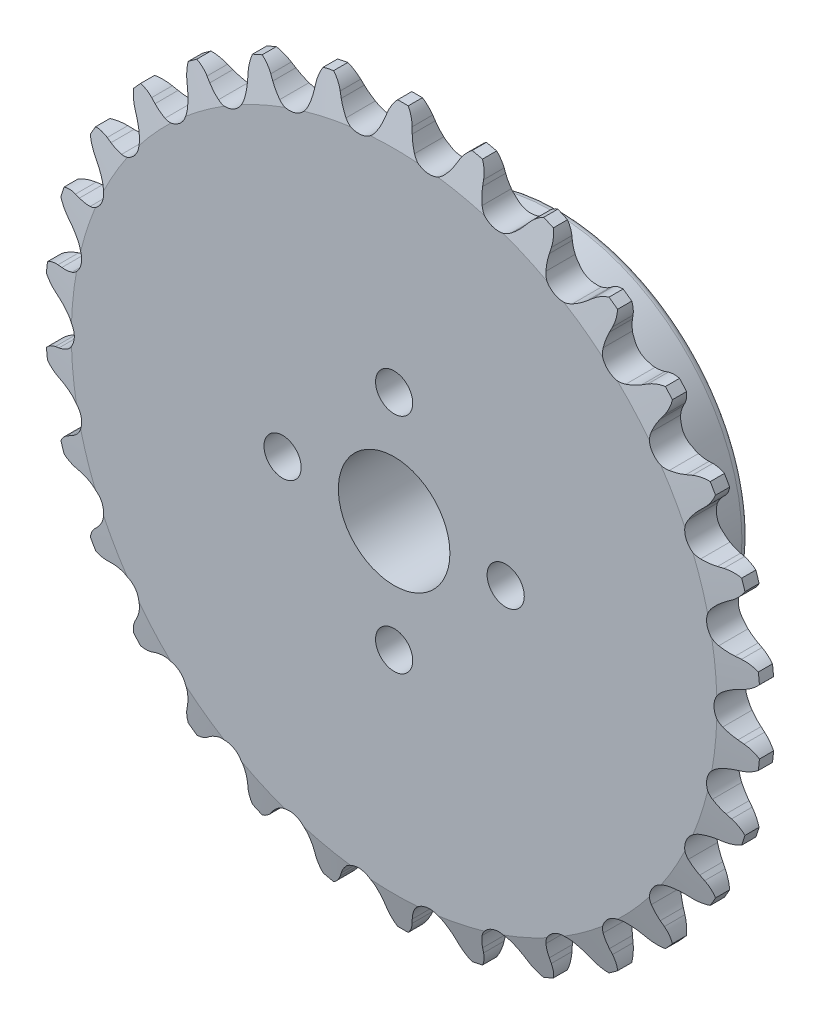
SolidWorks part; units mm, degrees
ref_plane "Front Plane" through (0, 0, 0) normal (0, 0, 1) x (1, 0, 0)
ref_plane "Top Plane" through (0, 0, 0) normal (0, 1, 0) x (1, 0, 0)
ref_plane "Right Plane" through (0, 0, 0) normal (1, 0, 0) x (0, 0, -1)
sketch "Sketch0" plane through (0, 0, 0) normal (0, 0, 1) x (1, 0, 0)
  line L0 (4.7625, -45.3122) -> (0, 0) construction
  line L1 (0, 0) -> (14.0794, -43.3318) construction
  line L2 (0, 0) -> (-4.7625, -45.3122) construction
  line L3 (4.7625, -45.3122) -> (14.0794, -43.3318) construction
  line L4 (4.7625, -45.3122) -> (-4.7625, -45.3122) construction
  line L5 (8.0084, -45.7133) -> (7.6941, -45.0929)
  line L6 (4.7625, -45.3122) -> (0, -45.8127) construction
  line L7 (1.6709, -46.3794) -> (1.8494, -45.7072)
  line L8 (0, -45.3122) -> (0, -48.1697) construction
  line L9 (6.6305, -43.5702) -> (1.7903, -48.0838) construction
  line L10 (0, 0) -> (0, -45.3122) construction
  line L11 (7.6941, -45.0929) -> (1.7903, -48.0838) construction
  line L12 (0, -48.1697) -> (0, -48.7448) construction
  line L13 (11.7191, -43.8335) -> (8.0084, -45.7133) construction
  circle A0 centre (0, 0) radius 48.1697 construction
  circle A1 centre (0, 0) radius 45.5618 construction
  arc A2 (-2.5649, -49.4663) -> (12.7935, -47.852) centre (0, 0) ccw
  circle A3 centre (0, 0) radius 48.7448 construction
  circle A4 centre (4.7625, -45.3122) radius 2.54 construction
  arc A7 (6.6305, -43.5702) -> (2.5731, -43.9967) centre (4.7625, -45.3122) ccw
  circle A8 centre (4.7625, -45.3122) radius 2.5542 construction
  arc A9 (8.0084, -45.7133) -> (12.7935, -47.852) centre (11.7191, -43.8335) ccw
  arc A10 (7.6941, -45.0929) -> (6.6305, -43.5702) centre (1.7903, -48.0838) ccw
  arc A11 (1.6709, -46.3794) -> (-2.5649, -49.4663) centre (-2.3495, -45.3122) cw
  arc A12 (1.8494, -45.7072) -> (2.5731, -43.9967) centre (8.246, -47.4053) cw
  dimension "D1" = 2.5542
  dimension "R" = 2.5542
sketch "Sketch1" plane through (0, 0, 0) normal (1, 0, 0) x (0, 0, -1)
  line L0 (2.1336, 0) -> (-2.1336, 0)
  line L1 (-2.1336, 0) -> (-2.1336, 43.4072)
  line L2 (-2.1336, 43.4072) -> (-0.943, 48.1697)
  line L3 (-0.943, 48.1697) -> (0.943, 48.1697)
  line L4 (0.943, 48.1697) -> (2.1336, 43.4072)
  line L5 (2.1336, 43.4072) -> (2.1336, 0)
  line L7 (0, 48.1697) -> (0, 0) construction
  line L8 (-2.1336, 43.4072) -> (2.1336, 43.4072) construction
  line L9 (0, 48.1697) -> (0, -48.1697) construction
  line L10 (-2.1336, 43.4072) -> (-2.1336, 48.1697) construction
  line L11 (-2.1336, 48.1697) -> (-0.943, 48.1697) construction
  line L12 (0.943, 48.1697) -> (2.1336, 48.1697) construction
  line L13 (2.1336, 48.1697) -> (2.1336, 43.4072) construction
revolve "Revolve1" add sketch "Sketch1" angle 360 mid plane about L0
extrude "Cut-Extrude1" cut sketch "Sketch0" against normal through all and the other way through all
pattern_circular "CirPattern1" count 30 over 360 about axis through (0, 0, -2.1336) along (0, 0, -1) of "Cut-Extrude1"
sketch "Sketch2" plane through (0, 0, 0) normal (0, 0, 1) x (1, 0, 0)
  circle A0 centre (0, 0) radius 7.5 construction
  circle A1 centre (0, 0) radius 30.1625
  circle A2 centre (0, 0) radius 48.133 construction
  dimension "Bore" = 15
  dimension "Hub Dia." = 60.325
  dimension "OD" = 96.266
sketch "Sketch7" plane through (0, 0, -2.1336) normal (0, 0, -1) x (-1, 0, 0)
  circle A0 centre (0, 0) radius 25.5
  dimension "D1" = 51
extrude "Boss-Extrude1" add sketch "Sketch7" along normal blind 18
sketch "Sketch3" plane through (0, 0, 0) normal (0, 0, 1) x (1, 0, 0)
  circle A0 centre (0, 0) radius 7.5 construction
  circle A1 centre (0, 0) radius 7.5
  circle A2 centre (0, 0) radius 48.133 construction
  circle A3 centre (0, 0) radius 48.133
extrude "Cut-Extrude2" cut sketch "Sketch3" along normal through all and the other way through all flip side to cut
sketch "Sketch4" plane through (0, 0, 2.1336) normal (0, 0, 1) x (1, 0, 0)
  circle A0 centre (0, 0) radius 15 construction
  circle A2 centre (0, 0) radius 15 construction
  dimension "D1" = 30
  dimension "D2" = 30
hole_wizard "Tap Drill for M6x1.0 Tap1" positions "Sketch5" profile "Sketch6" hole size "M6x1.0" standard "ANSI Metric" end condition through all
sketch "Sketch5" plane through (0, 0, 2.1336) normal (0, 0, 1) x (1, 0, 0)
  circle A0 centre (0, 0) radius 15 construction
  point P0 (0, 15)
sketch "Sketch6" plane through (0, 15, 2.1336) normal (1, 0, 0) x (0, -1, 0)
  line L0 (0, 0) -> (0, 22.2672)
  line L1 (0, 22.2672) -> (2.5, 22.2672)
  line L2 (2.5, 22.2672) -> (2.5, 0)
  line L5 (2.5, 0) -> (0, 0)
  line L11 (0, -6.35) -> (0, 107.95) construction
  dimension "Thru Hole Dia." = 5
  dimension "Thru Hole Depth" = 22.2672
pattern_circular "CirPattern2" count 4 over 360 about axis through (0, 0, 2.1336) along (0, 0, 1) of "Tap Drill for M6x1.0 Tap1"
fillet "Fillet1" radius 1 2 edges at (-25.5, 0, -20.1336) (-25.5, 0, -2.1336)
sketch "Sketch8" plane through (0, 0, -20.1336) normal (0, 0, -1) x (-1, 0, 0)
  circle A0 centre (0, 0) radius 10.0148
  dimension "D1" = 20.0295
extrude "Cut-Extrude3" [suppressed] cut sketch "Sketch8" against normal through all
sketch "Sketch9" plane through (0, 0, -20.1336) normal (0, 0, -1) x (-1, 0, 0)
  circle A0 centre (0, 0) radius 12
  dimension "D1" = 24
extrude "Cut-Extrude4" [suppressed] cut sketch "Sketch9" against normal blind 5
sketch "Sketch10" [suppressed] plane through (0, 0, 2.1336) normal (0, 0, 1) x (1, 0, 0)
  circle A0 centre (0, 0) radius 12
  dimension "D1" = 24
extrude "Cut-Extrude5" [suppressed] cut sketch "Sketch10" against normal blind 5
equation "\"360/N@Sketch0\" = 360/\"Teeth@CirPattern1\""
equation "\"Ds@Sketch0\" = 1.005 * \"Dr@Sketch0\" + 0.003"
equation "\"R@Sketch0\" = 1/2 * \"Ds@Sketch0\""
equation "\"A@Sketch0\" = 35 +  ( 60 / \"Teeth@CirPattern1\" ) "
equation "\"B@Sketch0\" = 18 -  ( 56 / \"Teeth@CirPattern1\" )"
equation "\"ac@Sketch0\" = 0.8 * \"Dr@Sketch0\""
equation "\"ab@Sketch0\" = 1.4 * \"Dr@Sketch0\""
equation "\"J@Sketch0\" = 0.3 * \"Pitch@Sketch0\""
equation "\"h@Sketch1\" = \"Pitch@Sketch0\" / 2"
equation "\"g@Sketch1\" = \"h@Sketch1\" / 4"
